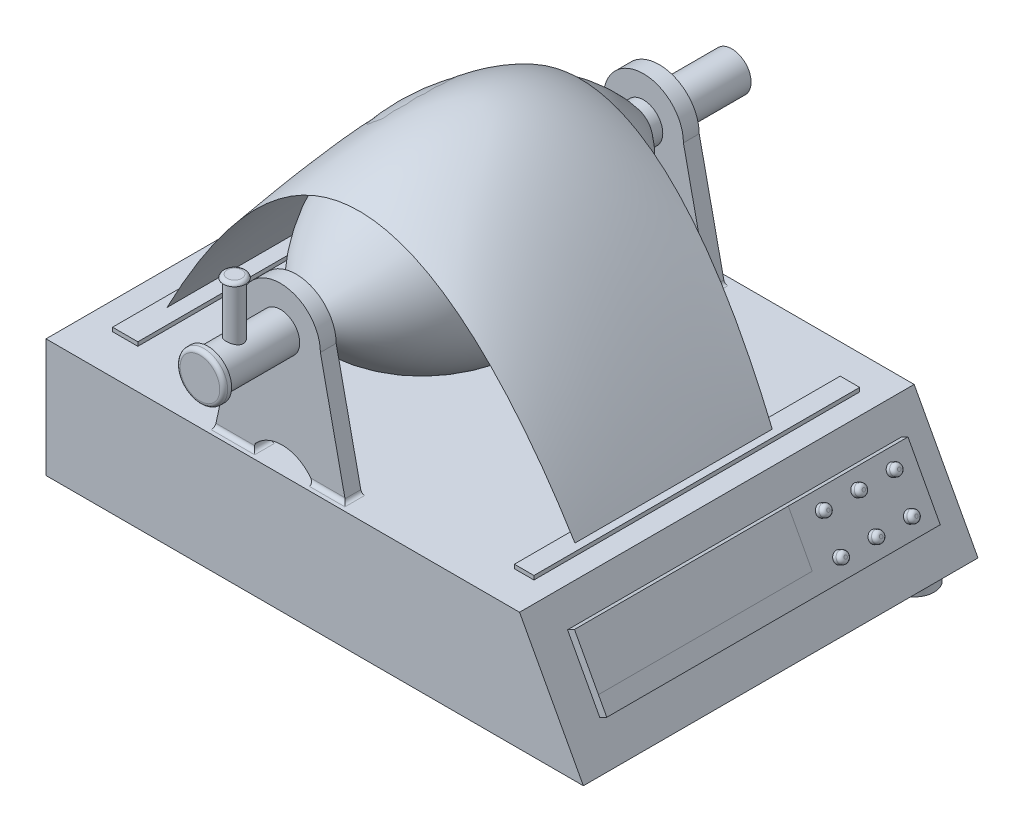
SolidWorks part; units mm, degrees
ref_plane "Front Plane" through (0, 0, 0) normal (0, 0, 1) x (1, 0, 0)
ref_plane "Top Plane" through (0, 0, 0) normal (0, 1, 0) x (1, 0, 0)
ref_plane "Right Plane" through (0, 0, 0) normal (1, 0, 0) x (0, 0, -1)
sketch "Sketch1" plane through (0, 0, 0) normal (0, 0, 1) x (1, 0, 0)
  line L0 (76.2, 19.05) -> (96.7454, -19.05)
  line L1 (-76.2, 19.05) -> (76.2, 19.05)
  line L2 (-76.2, 19.05) -> (-76.2, -19.05)
  line L3 (-76.2, -19.05) -> (76.2, -19.05)
  line L4 (76.2, 19.05) -> (76.2, -19.05)
  line L5 (-76.2, 19.05) -> (76.2, -19.05) construction
  line L6 (-76.2, -19.05) -> (76.2, 19.05) construction
  line L7 (96.7454, -19.05) -> (76.2, -19.05)
  point P0 (0, 0)
  dimension "D1" = 152.4
  dimension "D2" = 38.1
extrude "Boss-Extrude1" add sketch "Sketch1" along normal mid plane 127 contours L4 L1 L2 L3 | L7 L0 L4 region at (0, 0, 0) region at (83.0485, -6.35, 0)
sketch "Sketch2" plane through (0, 0, 63.5) normal (0, 0, 1) x (1, 0, 0)
  line L0 (-76.2, 19.05) -> (76.2, 19.05) construction
  line L2 (-16.1669, 19.05) -> (-12.7835, 19.05)
  line L6 (9.5629, 56.8545) -> (17.7085, 19.05)
  line L7 (17.7085, 19.05) -> (9.5629, 19.05)
  line L8 (-3.302, 56.8545) -> (-3.302, -30.1769) construction
  line L9 (-24.3125, 19.05) -> (-16.1669, 19.05)
  line L10 (-16.1669, 56.8545) -> (-24.3125, 19.05)
  line L11 (7.2786, 19.05) -> (9.5629, 19.05)
  arc A0 (9.5629, 56.8545) -> (-16.1669, 56.8545) centre (-3.302, 56.8545) ccw
  circle A1 centre (-3.302, 56.8545) radius 5.5813
  arc A2 (-12.7835, 19.05) -> (7.2786, 19.05) centre (-2.7525, 13.4031) cw
  dimension "D1" = 3.302
extrude "Boss-Extrude2" add sketch "Sketch2" against normal blind 5.08 from offset 2.54 offset against normal yes
ref_plane "Plane1" through (-3.302, 0, 0) normal (1, 0, 0) x (0, 0, -1)
sketch "Sketch4" plane through (-3.302, 0, 0) normal (1, 0, 0) x (0, 0, -1)
  line L0 (-94.1348, 56.2137) -> (105.9784, 56.2137) construction
  line L1 (-84.3174, 56.2137) -> (-84.3174, 50.0009)
  line L2 (-84.3174, 50.0009) -> (-52.6366, 50.0009)
  line L3 (0, 0) -> (0, 104.6567) construction
  line L4 (84.3174, 56.2137) -> (84.3174, 50.0009)
  line L5 (84.3174, 50.0009) -> (52.6366, 50.0009)
  line L6 (-84.3174, 56.2137) -> (84.3174, 56.2137)
  arc A0 (-52.6366, 50.0009) -> (52.6366, 50.0009) centre (0, 90.8468) ccw
revolve "Revolve2" add sketch "Sketch4" angle 360 about L6
mirror "Mirror1" about plane through (0, 0, 0) normal (0, 0, 1) of "Boss-Extrude2"
sketch "Sketch5" plane through (0, 0, 84.3174) normal (0, 0, 1) x (1, 0, 0)
  circle A0 centre (-3.302, 56.2137) radius 7.6492
extrude "Boss-Extrude3" add sketch "Sketch5" along normal blind 2.54
sketch "Sketch6" plane through (0, 19.05, 0) normal (0, 1, 0) x (1, 0, 0)
  line L1 (69.5376, 52.6366) -> (63.2572, 52.6366)
  line L2 (69.5376, 52.6366) -> (69.5376, -52.2085)
  line L3 (69.5376, -52.2085) -> (63.2572, -52.2085)
  line L4 (63.2572, 52.6366) -> (63.2572, -52.2085)
  line L5 (-67.4666, 52.6366) -> (-59.3254, 52.6366)
  line L6 (-67.4666, 52.6366) -> (-67.4666, -50.8129)
  line L7 (-67.4666, -50.8129) -> (-59.3254, -50.8129)
  line L8 (-59.3254, 52.6366) -> (-59.3254, -50.8129)
extrude "Boss-Extrude4" add sketch "Sketch6" along normal blind 1.27
sketch "Sketch7" plane through (0, 20.32, 0) normal (0, 1, 0) x (1, 0, 0)
  line L0 (67.1088, 26.9205) -> (67.1088, -36.5795)
  line L1 (-64.1919, 26.9205) -> (-64.1919, -36.5795)
  dimension "D1" = 63.5
  dimension "D2" = 63.5
sketch "Sketch8" plane through (-3.302, 0, 0) normal (1, 0, 0) x (0, 0, -1)
  arc A0 (-36.8156, 78.3708) -> (34.2926, 79.6637) centre (-0.3093, 26.6496) cw
  dimension "D1" = 71.12
surface "Surface-Loft1" start constraint default end constraint default
sketch "Sketch10" plane through (0, -19.05, 0) normal (0, -1, 0) x (1, 0, 0)
  circle A0 centre (-62.0008, 50.8256) radius 6.3388
  circle A1 centre (83.4878, 50.8256) radius 6.3388
  circle A2 centre (86.5483, -53.2294) radius 6.3388
  circle A3 centre (-64.8258, -54.8773) radius 6.3388
extrude "Boss-Extrude5" add sketch "Sketch10" along normal blind 6.35
sketch "Sketch11" plane through (66.9921, 36.1254, 0) normal (0.8802, 0.4746, 0) x (0, 0, -1)
  line L0 (-52.4721, -28.7073) -> (54.8501, -28.7073)
  line L5 (54.8501, -28.7073) -> (54.8501, -50.6119)
  line L6 (-52.4721, -50.6119) -> (54.8501, -50.6119)
  line L7 (-52.4721, -28.7073) -> (-52.4721, -50.6119)
extrude "Boss-Extrude6" add sketch "Sketch11" along normal blind 2.54
sketch "Sketch12" plane through (69.2278, 37.331, 0) normal (0.8802, 0.4746, 0) x (0, 0, -1)
  line L1 (-52.4721, -28.7073) -> (16.3312, -28.7073)
  line L2 (-52.4721, -28.7073) -> (-52.4721, -44.9658)
  line L3 (-52.4721, -44.9658) -> (16.3312, -44.9658)
  line L4 (16.3312, -28.7073) -> (16.3312, -44.9658)
split line "Split Line1"
sketch "Sketch14" plane through (66.9921, 36.1254, 0) normal (0.8802, 0.4746, 0) x (0, 0, -1)
  circle A0 centre (24.7123, -33.5791) radius 1.776
  circle A1 centre (36.1084, -33.5791) radius 1.776
  circle A2 centre (47.5046, -33.5791) radius 1.776
  circle A3 centre (24.7123, -45.2713) radius 1.776
  circle A4 centre (36.1084, -45.2713) radius 1.776
  circle A5 centre (47.5046, -45.2713) radius 1.776
extrude "Boss-Extrude7" add sketch "Sketch14" along normal blind 5.08
fillet "Fillet2" radius 1.27 6 edges at (92.1079, 0.2529, -36.1084) (92.1079, 0.2529, -47.5046) (86.5583, 10.5441, -47.5046) (86.5583, 10.5441, -36.1084) (86.5583, 10.5441, -24.7123) (92.1079, 0.2529, -24.7123)
sketch "Sketch15" plane through (0, 0, 0) normal (0, 1, 0) x (1, 0, 0)
  circle A0 centre (-3.2034, -75.829) radius 2.7619
extrude "Boss-Extrude8" add sketch "Sketch15" along normal blind 22.86 from offset 55.88
sketch "Sketch16" plane through (0, 78.74, 0) normal (0, 1, 0) x (1, 0, 0)
  circle A0 centre (-3.2034, -75.829) radius 3.6053
extrude "Boss-Extrude9" add sketch "Sketch16" along normal blind 1.016
fillet "Fillet3" radius 1.27 1 edges at (4.3472, 56.2137, 86.8574)
fillet "Fillet4" radius 1.27 1 edges at (-3.2034, 79.756, 79.4344)
fillet "Fillet5" radius 1.27 8 edges at (-18.548, 19.05, -55.88) (-12.7835, 19.05, -58.42) (12.4935, 19.05, -55.88) (17.7085, 19.05, -58.42) (12.4935, 19.05, 60.96) (17.7085, 19.05, 58.42) (-18.548, 19.05, 60.96) (-12.7835, 19.05, 58.42)
